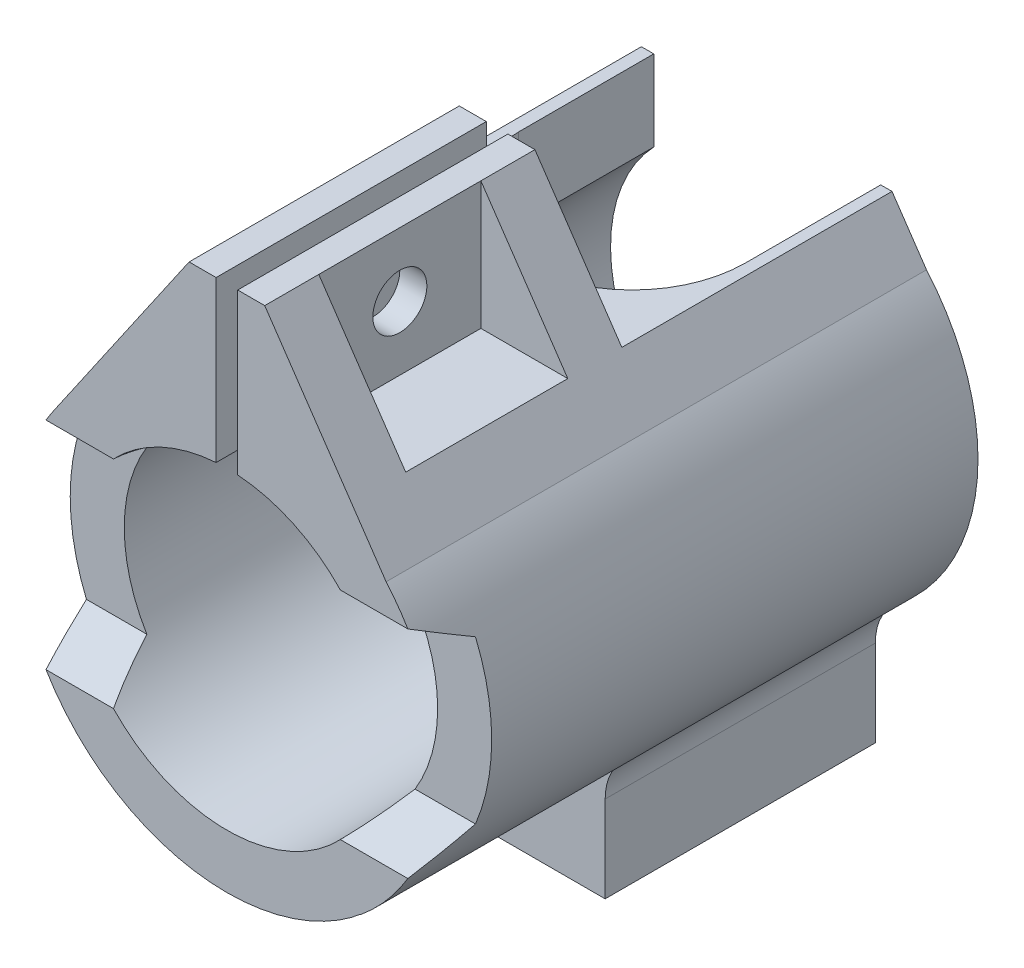
SolidWorks part; units mm, degrees
material "ABS"
ref_plane "Front Plane" through (0, 0, 0) normal (0, 0, 1) x (1, 0, 0)
ref_plane "Top Plane" through (0, 0, 0) normal (0, 1, 0) x (1, 0, 0)
ref_plane "Right Plane" through (0, 0, 0) normal (1, 0, 0) x (0, 0, -1)
sketch "Sketch1" plane through (0, 0, 0) normal (0, 0, 1) x (1, 0, 0)
  line L0 (0, 29.2916) -> (0, 14.5) construction
  line L1 (1, 29.2916) -> (1, 14.4655)
  line L2 (-1, 29.2916) -> (-1, 14.4655)
  line L4 (0, -55) -> (0, 55) construction
  line L6 (-3.5, 29.2916) -> (-16.0582, 11.0628)
  line L7 (3.5, 29.2916) -> (14.7337, 12.7738)
  line L8 (10, -19.5) -> (10, -27.5)
  line L9 (10, -27.5) -> (-10, -27.5)
  line L10 (-3.5, 29.2916) -> (-1, 29.2916)
  line L11 (1, 44.1585) -> (1, -43.2542) construction
  line L12 (1, 29.2916) -> (3.5, 29.2916)
  line L13 (0, 44.1585) -> (0, -43.2542) construction
  line L14 (0, -14.5) -> (0, -19.5) construction
  line L15 (-1, 44.1585) -> (-1, -43.2542) construction
  line L16 (-10, -19.5) -> (-10, -27.5)
  arc A0 (-1, 14.4655) -> (1, 14.4655) centre (0, 0) ccw
  arc A1 (19.5, 0) -> (14.7337, 12.7738) centre (0, 0) ccw
  arc A2 (0, -19.5) -> (19.5, 0) centre (0, 0) ccw
  arc A3 (10, -19.5) -> (12.4557, -15.0035) centre (15.3445, -19.5) cw
  arc A4 (-16.0582, 11.0628) -> (0, -19.5) centre (0, 0) ccw
  arc A5 (-10, -19.5) -> (-11.754, -15.5593) centre (-15.3036, -19.5) ccw
  dimension "D1" = 29
  dimension "D2" = 10
  dimension "D5" = 20
  dimension "D6" = 8
  dimension "D3" = 1
  dimension "D4" = 1
extrude "Boss-Extrude1" add sketch "Sketch1" against normal blind 50 contours L6 A4 A2 A3 A1 L7 L12 L1 A0 L2 L10 | A5 L16 L9 L8 A3 A2 A4 region at (2.25, 28.667, 0) region at (-0.0012, -22.9481, 0)
ref_plane "Plane1" through (14.5, 0, 0) normal (1, 0, 0) x (0, 0, -1)
ref_plane "Plane2" through (3.5, 0, 0) normal (1, 0, 0) x (0, 0, -1)
sketch "Sketch4" plane through (3.5, 0, 0) normal (1, 0, 0) x (0, 0, -1)
  line L5 (20, 29.2916) -> (20, 17.4655)
  line L11 (5, 29.2916) -> (5, 17.4655)
  line L13 (5, 29.2916) -> (5, 12.7738) construction
  line L14 (20, 29.2916) -> (20, 12.7738) construction
  line L15 (20, 17.4655) -> (5, 17.4655)
  line L19 (5, 29.2916) -> (20, 29.2916)
  dimension "D4" = 15
extrude "Cut-Extrude3" cut sketch "Sketch4" along normal through all
mirror "Mirror1" about plane through (0, 0, 0) normal (1, 0, 0) of "Cut-Extrude3"
sketch "Sketch5" plane through (3.5, 0, 0) normal (1, 0, 0) x (0, 0, -1)
  line L0 (12.5, 29.2916) -> (12.5, 17.4655) construction
  line L1 (20, 29.2916) -> (5, 29.2916) construction
  line L2 (20, 17.4655) -> (5, 17.4655) construction
  circle A1 centre (12.5, 23.3786) radius 2.5
extrude "Cut-Extrude4" cut sketch "Sketch5" against normal through all and the other way through all
ref_plane "Plane4" through (0, 14.5, 0) normal (0, 1, 0) x (1, 0, 0)
sketch "Sketch8" plane through (0, 14.5, 0) normal (0, 1, 0) x (1, 0, 0)
  line L0 (0, 52.4118) -> (0, -2.548) construction
  line L1 (0, -27.5) -> (0, 27.5) construction
  line L2 (-19.5, 50) -> (-1, 50) construction
  line L3 (-19.5, 37.5) -> (19.5, 37.5) construction
  line L4 (-10.5, 37.5) -> (-10.5, 50)
  line L5 (-10.5, 50) -> (-1, 50)
  line L6 (10.5, 50) -> (10.5, 37.5)
  line L7 (-1, 50) -> (-1, 27.0477)
  line L8 (1, 50) -> (1, 27.0477)
  line L9 (1, 50) -> (1, 0) construction
  line L10 (1, 50) -> (19.5, 50) construction
  line L11 (-19.5, 50) -> (19.5, 50) construction
  line L12 (1, 50) -> (10.5, 50)
  arc A0 (-10.5, 37.5) -> (-1, 27.0477) centre (0, 37.5) ccw
  arc A1 (1, 27.0477) -> (10.5, 37.5) centre (0, 37.5) ccw
  dimension "D1" = 12.5
sketch "Sketch9" plane through (3.5, 0, 0) normal (1, 0, 0) x (0, 0, -1)
  line L0 (5, 17.4655) -> (50, 17.4655) construction
  line L1 (50, 29.2916) -> (50, 11.0628) construction
  line L3 (25, 29.2916) -> (50, 29.2916)
  line L4 (25, 17.4655) -> (25, 29.2916)
  line L5 (25, 17.4655) -> (25, 29.2916)
  line L6 (50, 29.2916) -> (50, 17.4655)
  line L7 (50, 17.4655) -> (25, 17.4655)
  dimension "D1" = 5
extrude "Cut-Extrude8" cut sketch "Sketch9" against normal through all and the other way through all
extrude "Cut-Extrude9" cut sketch "Sketch8" against normal up to surface and the other way up to next (2.9655 mm away) up to face at (0, -0.0173, -25)
ref_plane "Plane5" through (0, 0, -37.5) normal (0, 0, 1) x (1, 0, 0)
sketch "Sketch10" plane through (0, 0, -37.5) normal (0, 0, 1) x (1, 0, 0)
  line L0 (0, 14.5) -> (0, -22.2883) construction
  line L1 (21.45, 14.5) -> (-21.45, 14.5) construction
  line L2 (0, -27.5) -> (0, 27.5) construction
  line L3 (-7, -12.6984) -> (7, -12.6984)
  line L5 (-7, -12.6984) -> (-7, -14.9416)
  line L7 (7, -12.6984) -> (7, -14.9416)
  arc A3 (-1.1379, 16.4607) -> (1.1379, 16.4607) centre (0, 0) ccw
  arc A4 (-7, -14.9416) -> (7, -14.9416) centre (0, 0) ccw
  dimension "D1" = 2
extrude "Cut-Extrude10" cut sketch "Sketch10" against normal through all and the other way blind 13
sketch "Sketch11" plane through (0, 0, 0) normal (1, 0, 0) x (0, 0, -1)
  line L0 (-2.5449, 0) -> (0, 0) construction
  line L1 (21.45, 0) -> (-21.45, 0) construction
  line L2 (-2.5449, -10) -> (0, -10) construction
  line L7 (-2.5449, 10) -> (0, 10) construction
  line L8 (0, 10) -> (0, -10)
  line L9 (0, 21.45) -> (0, -21.45) construction
  line L10 (5, 7.5) -> (5, -7.5)
  line L11 (-2.5449, -7.5) -> (5, -7.5) construction
  line L13 (-2.5449, 7.5) -> (5, 7.5) construction
  line L14 (0, 10) -> (5, 7.5)
  line L15 (5, -7.5) -> (0, -10)
  line L16 (-2.5449, -7.5) -> (52.5147, -7.5) construction
  line L17 (-2.5449, 10) -> (52.5147, 10) construction
  line L18 (5, 10) -> (5, -10) construction
  line L19 (-2.5449, 7.5) -> (52.5147, 7.5) construction
  line L21 (-2.5449, -10) -> (52.5147, -10) construction
  line L22 (5, 0) -> (52.5147, 0) construction
  line L23 (-2.5449, 0) -> (52.5147, 0) construction
  line L24 (5, 0) -> (52.5147, 0)
  dimension "D1" = 10
  dimension "D2" = 10
  dimension "D3" = 5
  dimension "D4" = 7.5
  dimension "D5" = 7.5
extrude "Cut-Extrude11" cut sketch "Sketch11" against normal through all and the other way through all contours L15 L10 L14 L8 region at (0, 0, -2.381)
sketch "Sketch13" plane through (0, -27.5, 0) normal (0, -1, 0) x (1, 0, 0)
  line L0 (4.106, -37.5) -> (-4.106, -37.5) construction
  line L1 (0, -31.0842) -> (-5.5563, -34.2921)
  line L2 (-5.5563, -34.2921) -> (-5.5563, -40.7079)
  line L3 (-5.5563, -40.7079) -> (0, -43.9158)
  line L4 (0, -43.9158) -> (5.5563, -40.7079)
  line L5 (5.5563, -40.7079) -> (5.5563, -34.2921)
  line L6 (5.5563, -34.2921) -> (0, -31.0842)
  line L7 (0, -27.5) -> (0, 27.5) construction
  circle A0 centre (0, -37.5) radius 5.5563 construction
extrude "Cut-Extrude15" cut sketch "Sketch13" against normal up to next
sketch "Sketch14" plane through (0, -27.5, 0) normal (0, -1, 0) x (1, 0, 0)
  line L1 (5.5563, -40.7079) -> (5.5562, -34.2921)
  line L2 (5.5562, -34.2921) -> (0, -31.0842)
  line L3 (0, -31.0842) -> (-5.5563, -34.2921)
  line L4 (-5.5563, -34.2921) -> (-5.5562, -40.7079)
  line L5 (-5.5562, -40.7079) -> (0, -43.9158)
  line L6 (0, -43.9158) -> (5.5563, -40.7079)
  circle A0 centre (0, -37.5) radius 5.5563 construction
  circle A1 centre (0, -37.5) radius 3.375
extrude "Boss-Extrude2" add sketch "Sketch14" against normal blind 2.5
sketch "Sketch15" plane through (0, 0, 0) normal (0, 0, 1) x (1, 0, 0)
  line L0 (-19.5, 0) -> (-19.5, -27.5)
  line L1 (-19.5, -27.5) -> (19.5, -27.5)
  line L2 (19.5, -27.5) -> (19.5, 0)
  arc A0 (-19.5, 0) -> (19.5, 0) centre (0, 0) ccw
extrude "Cut-Extrude17" cut sketch "Sketch15" against normal blind 25
